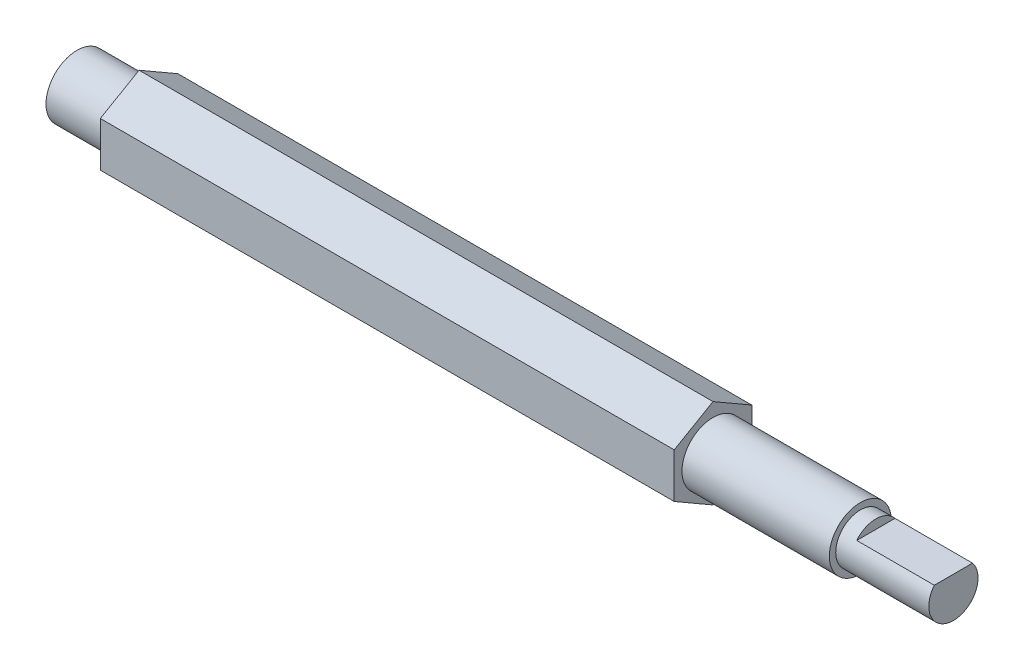
SolidWorks part; units mm, degrees
material "Chrome Stainless Steel"
ref_plane "Front Plane" through (0, 0, 0) normal (0, 0, 1) x (1, 0, 0)
ref_plane "Top Plane" through (0, 0, 0) normal (0, 1, 0) x (1, 0, 0)
ref_plane "Right Plane" through (0, 0, 0) normal (1, 0, 0) x (0, 0, -1)
sketch "Sketch1" plane through (0, 0, 0) normal (0, 0, 1) x (1, 0, 0)
  line L0 (0, 2) -> (-4, 2)
  line L1 (-4, 2) -> (-4, 0)
  line L2 (-6.1852, 0) -> (29.7037, 0) construction
  line L4 (46.5, 2) -> (37, 2)
  line L5 (37, 2) -> (37, 2.5)
  line L6 (37, 2.5) -> (0, 2.5)
  line L7 (0, 2.5) -> (0, 2)
  line L8 (-4, 0) -> (52.5, 0)
  line L9 (46.5, 2) -> (46.5, 1.5875)
  line L10 (46.5, 1.5875) -> (52.5, 1.5875)
  line L11 (52.5, 1.5875) -> (52.5, 0)
  point P13 (0, 0)
  point P14 (51.0209, 1.5875)
  dimension "D1" = 5
  dimension "D2" = 4
  dimension "D3" = 4
  dimension "D4" = 9.5
  dimension "D5" = 4
  dimension "D6" = 37
  dimension "D7" = 3.175
  dimension "D8" = 6
revolve "Revolve1" add sketch "Sketch1" angle 360 about L2
sketch "Sketch2" plane through (0, 0, 0) normal (1, 0, 0) x (0, 0, -1)
  line L1 (0, 2.8868) -> (-2.5, 1.4434)
  line L2 (-2.5, 1.4434) -> (-2.5, -1.4434)
  line L3 (-2.5, -1.4434) -> (0, -2.8868)
  line L4 (0, -2.8868) -> (2.5, -1.4434)
  line L5 (2.5, -1.4434) -> (2.5, 1.4434)
  line L6 (2.5, 1.4434) -> (0, 2.8868)
  circle A0 centre (0, 0) radius 2.5 construction
extrude "Boss-Extrude1" add sketch "Sketch2" along normal up to surface (37 mm away) up to face at (37, 0, 2.5)
ref_axis "Axis1" through (18.4956, 0, 0) along (-1, 0, 0)
ref_plane "Plane1" through (0, 1, 0) normal (0, 1, 0) x (1, 0, 0)
sketch "Sketch4" plane through (0, 1, 0) normal (0, 1, 0) x (1, 0, 0)
  line L0 (46.5, -2) -> (46.5, 2) construction
  line L1 (56.1557, 5.3208) -> (47.5, 5.3208)
  line L2 (56.1557, 5.3208) -> (56.1557, -5.3825)
  line L3 (56.1557, -5.3825) -> (47.5, -5.3825)
  line L4 (47.5, 5.3208) -> (47.5, -5.3825)
  dimension "D1" = 1
extrude "Cut-Extrude1" cut sketch "Sketch4" along normal through all
